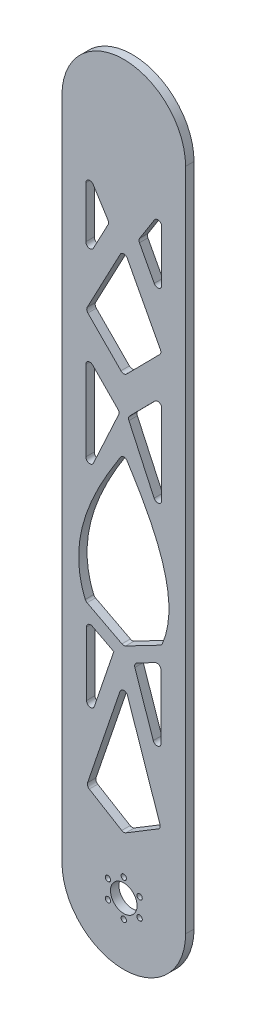
SolidWorks part; units mm, degrees
material "1060 Alloy"
ref_plane "Front Plane" through (0, 0, 0) normal (0, 0, 1) x (1, 0, 0)
ref_plane "Top Plane" through (0, 0, 0) normal (0, 1, 0) x (1, 0, 0)
ref_plane "Right Plane" through (0, 0, 0) normal (1, 0, 0) x (0, 0, -1)
sketch "Sketch2" plane through (0, 0, 0) normal (0, 0, 1) x (1, 0, 0)
  line L0 (0, 0) -> (0, 500) construction
  line L1 (-46.5, 0) -> (-46.5, 500)
  line L2 (46.5, 0) -> (46.5, 500)
  arc A0 (-46.5, 0) -> (46.5, 0) centre (0, 0) ccw
  arc A1 (46.5, 500) -> (-46.5, 500) centre (0, 500) ccw
  circle A2 centre (0, 500) radius 37.25 construction
  circle A3 centre (0, 0) radius 10
  circle A4 centre (0, 13.75) radius 2
  circle A5 centre (0, 0) radius 13.75 construction
  circle A6 centre (11.9078, 6.875) radius 2
  circle A7 centre (11.9078, -6.875) radius 2
  circle A8 centre (0, -13.75) radius 2
  circle A9 centre (-11.9078, -6.875) radius 2
  circle A10 centre (-11.9078, 6.875) radius 2
  point P3 (0, 250)
  point P27 (0, 0)
  dimension "D2" = 74.5
  dimension "D4" = 20
  dimension "D5" = 4
  dimension "D6" = 27.5
  dimension "D3" = 46.5
  dimension "D1" = 500
  dimension "D7" = 6
extrude "Boss-Extrude1" add sketch "Sketch2" along normal blind 6.35
sketch "Sketch4" plane through (0, 0, 6.35) normal (0, 0, 1) x (1, 0, 0)
  line L0 (0, 500) -> (0, 999.1647) construction
  line L29 (46.5, 500) -> (-46.5, 500) construction
  line L31 (28.0053, 59.376) -> (0, 42.4117)
  line L32 (0, 141.6934) -> (28.0053, 59.376)
  line L33 (-28.0053, 59.376) -> (0, 141.6934)
  line L34 (0, 42.4117) -> (-28.0053, 59.376)
  line L35 (-7.5, 156.9059) -> (-28.0053, 96.6336)
  line L36 (-28.0053, 167.5829) -> (-7.5, 156.9059)
  line L37 (-28.0053, 96.6336) -> (-28.0053, 167.5829)
  line L38 (28.0053, 167.5829) -> (7.5, 156.9059)
  line L39 (28.0053, 96.6336) -> (28.0053, 167.5829)
  line L40 (7.5, 156.9059) -> (28.0053, 96.6336)
  line L41 (0, 164.2751) -> (28.5505, 179.1412)
  line L42 (0, 164.2751) -> (-28.5505, 179.1412)
  line L43 (28.5505, 259.5868) -> (3, 314.9383)
  line L44 (28.5505, 340.7931) -> (28.5505, 259.5868)
  line L45 (3, 314.9383) -> (28.5505, 340.7931)
  line L46 (-3, 314.9383) -> (-28.5505, 340.7931)
  line L47 (-28.5505, 259.5868) -> (-3, 314.9383)
  line L48 (-28.5505, 340.7931) -> (-28.5505, 259.5868)
  line L49 (0, 423.1428) -> (-28.5505, 369.2462)
  line L50 (-28.5505, 369.2462) -> (0, 340.3557)
  line L51 (0, 340.3557) -> (28.5505, 369.2462)
  line L52 (0, 423.1428) -> (28.5505, 369.2462)
  line L53 (-28.5505, 462.0952) -> (-28.5505, 401.2902)
  line L54 (-11, 434.4215) -> (-28.5505, 462.0952)
  line L55 (-28.5505, 401.2902) -> (-11, 434.4215)
  line L56 (28.5505, 401.2902) -> (11, 434.4215)
  line L57 (28.5505, 462.0952) -> (28.5505, 401.2902)
  line L58 (11, 434.4215) -> (28.5505, 462.0952)
  arc A0 (46.5, 500) -> (-46.5, 500) centre (0, 500) ccw construction
  arc A1 (46.5, 500) -> (-46.5, 500) centre (0, 500) ccw construction
  spline S2 degree 3 poles (28.5505, 179.1412) (45.3203, 216.9857) (19.4301, 259.7903) (0, 290.0258) knots 0 0 0 0 1 1 1 1
  spline S3 degree 3 poles (-28.5505, 179.1412) (-45.3203, 216.9857) (-19.4301, 259.7903) (0, 290.0258) knots 0 0 0 0 1 1 1 1
extrude "Cut-Extrude1" cut sketch "Sketch4" against normal blind 10
fillet "Fillet3" radius 3 29 edges at (-11, 434.4215, 3.175) (-28.5505, 401.2902, 3.175) (28.5505, 401.2902, 3.175) (11, 434.4215, 3.175) (28.5505, 462.0952, 3.175) (-28.5505, 462.0952, 3.175) (0, 423.1428, 3.175) (-28.5505, 369.2462, 3.175) (28.5505, 369.2462, 3.175) (0, 340.3557, 3.175) (28.5505, 340.7931, 3.175) (-28.5505, 340.7931, 3.175) (-3, 314.9383, 3.175) (3, 314.9383, 3.175) (28.5505, 259.5868, 3.175) (-28.5505, 259.5868, 3.175) (28.5505, 179.1412, 3.175) (0, 290.0258, 3.175) (-28.5505, 179.1412, 3.175) (0, 164.2751, 3.175) (-28.0053, 96.6336, 3.175) (28.0053, 96.6336, 3.175) (7.5, 156.9059, 3.175) (-28.0053, 167.5829, 3.175) (28.0053, 167.5829, 3.175) (0, 141.6934, 3.175) (28.0053, 59.376, 3.175) (-28.0053, 59.376, 3.175) (0, 42.4117, 3.175)
equation "\"L1L\"=500"
equation "\"L1Thick\"=6.35"
equation "\"D1@Sketch2\"=\"L1L\""
equation "\"Harm-Drive-Outer\"=74.5"
equation "\"D2@Sketch2\"=\"Harm-Drive-Outer\""
equation "\"D1@Boss-Extrude1\"=\"L1Thick\""
